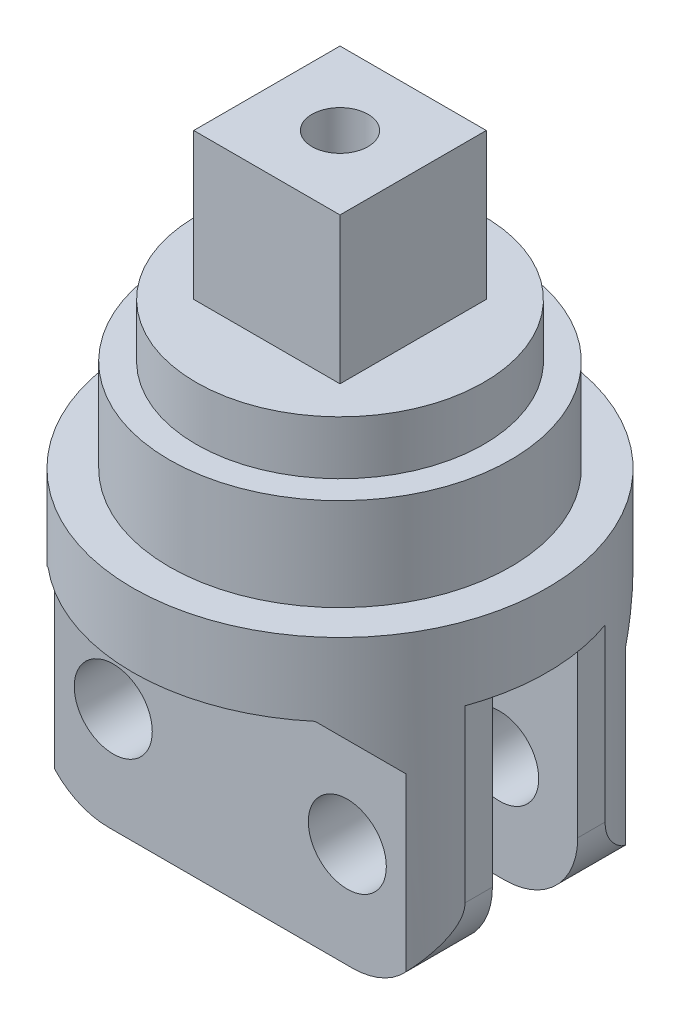
SolidWorks part; units mm, degrees
ref_plane "Спереди" through (0, 0, 0) normal (0, 0, 1) x (1, 0, 0)
ref_plane "Сверху" through (0, 0, 0) normal (0, 1, 0) x (1, 0, 0)
ref_plane "Справа" through (0, 0, 0) normal (1, 0, 0) x (0, 0, -1)
sketch "Эскиз9" plane through (0, 0, 0) normal (0, 1, 0) x (1, 0, 0)
  circle A0 centre (0, 0) radius 9
  dimension "D1" = 18
extrude "Бобышка-Вытянуть4" add sketch "Эскиз9" along normal blind 3
sketch "Эскиз10" plane through (0, 3, 0) normal (0, 1, 0) x (1, 0, 0)
  circle A0 centre (0, 0) radius 7
  dimension "D1" = 14
extrude "Бобышка-Вытянуть5" add sketch "Эскиз10" along normal blind 6
sketch "Эскиз11" plane through (0, 0, 0) normal (0, -1, 0) x (1, 0, 0)
  line L0 (0, -9.873) -> (0, 9.6847) construction
  line L1 (8, -4.5) -> (-8, -4.5)
  line L2 (8, -4.5) -> (8, -1.5)
  line L3 (8, -1.5) -> (-8, -1.5)
  line L4 (-8, -4.5) -> (-8, -1.5)
  line L5 (8, -4.5) -> (-8, -1.5) construction
  line L6 (8, -1.5) -> (-8, -4.5) construction
  line L7 (8, 1.5) -> (-8, 1.5)
  line L8 (8, 1.5) -> (8, 4.5)
  line L9 (8, 4.5) -> (-8, 4.5)
  line L10 (-8, 1.5) -> (-8, 4.5)
  line L11 (8, 1.5) -> (-8, 4.5) construction
  line L12 (8, 4.5) -> (-8, 1.5) construction
  line L13 (-8.6963, 0) -> (8.1785, 0) construction
  point P0 (0, -3)
  point P5 (0, 3)
  dimension "D1" = 3
  dimension "D2" = 3
  dimension "D3" = 3
  dimension "D4" = 16
  dimension "D5" = 16
extrude "Бобышка-Вытянуть6" add sketch "Эскиз11" along normal blind 10
sketch "Эскиз12" plane through (0, 0, 4.5) normal (0, 0, 1) x (1, 0, 0)
  line L0 (-4.4246, -5.7) -> (5.7426, -5.7) construction
  line L1 (7.7942, 0) -> (-7.7942, 0) construction
  line L2 (0, 0) -> (0, -8.684) construction
  circle A0 centre (-4.8, -5.7) radius 1.6
  circle A1 centre (4.8, -5.7) radius 1.6
  dimension "D3" = 3.2
  dimension "D1" = 5.7
  dimension "D2" = 9.6
extrude "Вырез-Вытянуть3" cut sketch "Эскиз12" against normal through all
sketch "Эскиз13" plane through (0, -10, 0) normal (0, -1, 0) x (1, 0, 0)
  circle A0 centre (0, 0) radius 9
  circle A1 centre (0, 0) radius 12.0355
extrude "Вырез-Вытянуть4" cut sketch "Эскиз13" against normal blind 30
fillet "Скругление1" radius 3 4 edges at (-8, -10, -2.8116) (8, -10, -2.8116) (8, -10, 2.8116) (-8, -10, 2.8116)
sketch "Эскиз14" plane through (0, 0, 0) normal (0, -1, 0) x (1, 0, 0)
  circle A0 centre (0, 0) radius 1.15
  dimension "D1" = 2.3
extrude "Вырез-Вытянуть5" cut sketch "Эскиз14" against normal blind 30
sketch "Эскиз15" plane through (0, 0, 0) normal (0, -1, 0) x (1, 0, 0)
  line L1 (11.2166, 1.75) -> (-11.2166, 1.75)
  line L2 (11.2166, 1.75) -> (11.2166, -1.75)
  line L3 (11.2166, -1.75) -> (-11.2166, -1.75)
  line L4 (-11.2166, 1.75) -> (-11.2166, -1.75)
  line L5 (11.2166, 1.75) -> (-11.2166, -1.75) construction
  line L6 (11.2166, -1.75) -> (-11.2166, 1.75) construction
  point P0 (0, 0)
  dimension "D1" = 3.5
extrude "Вырез-Вытянуть6" cut sketch "Эскиз15" along normal blind 20
sketch "Эскиз17" plane through (0, -10, 0) normal (0, -1, 0) x (1, 0, 0)
  circle A0 centre (0, 0) radius 12.0492
  circle A1 centre (0, 0) radius 8.5
  dimension "D1" = 17
extrude "Вырез-Вытянуть7" cut sketch "Эскиз17" against normal blind 20
sketch "Эскиз18" plane through (0, 9, 0) normal (0, 1, 0) x (1, 0, 0)
  circle A0 centre (0, 0) radius 9.5344
  circle A1 centre (0, 0) radius 5.9
  dimension "D1" = 11.8
extrude "Вырез-Вытянуть8" cut sketch "Эскиз18" against normal blind 2.2
sketch "Эскиз20" plane through (0, 9, 0) normal (0, 1, 0) x (1, 0, 0)
  line L1 (-3, 3) -> (3, 3)
  line L2 (-3, 3) -> (-3, -3)
  line L3 (-3, -3) -> (3, -3)
  line L4 (3, 3) -> (3, -3)
  line L5 (-3, 3) -> (3, -3) construction
  line L6 (-3, -3) -> (3, 3) construction
  circle A0 centre (0, 0) radius 1.15
  point P0 (0, 0)
  dimension "D1" = 6
  dimension "D2" = 6
extrude "Бобышка-Вытянуть7" add sketch "Эскиз20" along normal blind 6
chamfer "Фаска1" distance 2 angle 45 2 edges at (0, 0, -4.5) (0, 0, 4.5)
